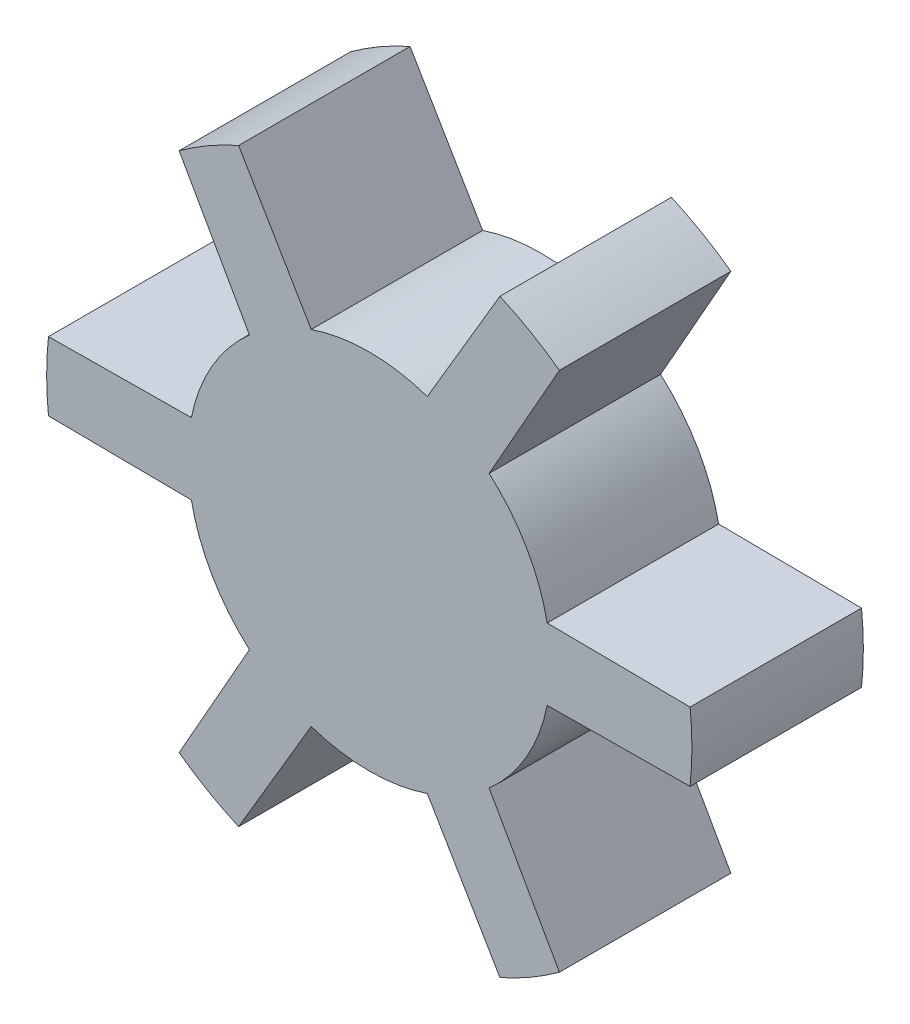
SolidWorks part; units mm, degrees
ref_plane "Płaszczyzna przednia" through (0, 0, 0) normal (0, 0, 1) x (1, 0, 0)
ref_plane "Płaszczyzna górna" through (0, 0, 0) normal (0, 1, 0) x (1, 0, 0)
ref_plane "Płaszczyzna prawa" through (0, 0, 0) normal (1, 0, 0) x (0, 0, -1)
sketch "Szkic1" plane through (0, 0, 0) normal (0, 0, 1) x (1, 0, 0)
  circle A0 centre (0, 0) radius 22.225
  circle A1 centre (0, 0) radius 12.5
  dimension "D1" = 44.45
  dimension "D2" = 25
extrude "Dodanie-wyciągnięcie1" add sketch "Szkic1" along normal blind 11.81
sketch "Szkic2" plane through (0, 0, 11.81) normal (0, 0, 1) x (1, 0, 0)
  line L0 (-4, -11.8427) -> (-9, -20.3212)
  line L1 (4, -11.8427) -> (9, -20.3212)
  circle A0 centre (0, 0) radius 12.5 construction
  circle A1 centre (0, 0) radius 22.225 construction
  arc A2 (-4, -11.8427) -> (4, -11.8427) centre (0, 0) ccw
  arc A3 (-9, -20.3212) -> (9, -20.3212) centre (0, 0) ccw
  dimension "D1" = 4
  dimension "D2" = 4
  dimension "D3" = 9
  dimension "D4" = 9
extrude "Wytnij-wyciągnięcie1" cut sketch "Szkic2" against normal up to next
sketch "Szkic3" plane through (0, 0, 11.81) normal (0, 0, 1) x (1, 0, 0)
  circle A0 centre (0, 0) radius 12.5
  arc A1 (4, -11.8427) -> (-4, -11.8427) centre (0, 0) ccw construction
extrude "Dodanie-wyciągnięcie2" add sketch "Szkic3" against normal blind 11.81
pattern_circular "Szyk kołowy1" count 6 over 360 about axis through (0, 0, 11.81) along (0, 0, 1) of "Wytnij-wyciągnięcie1"
